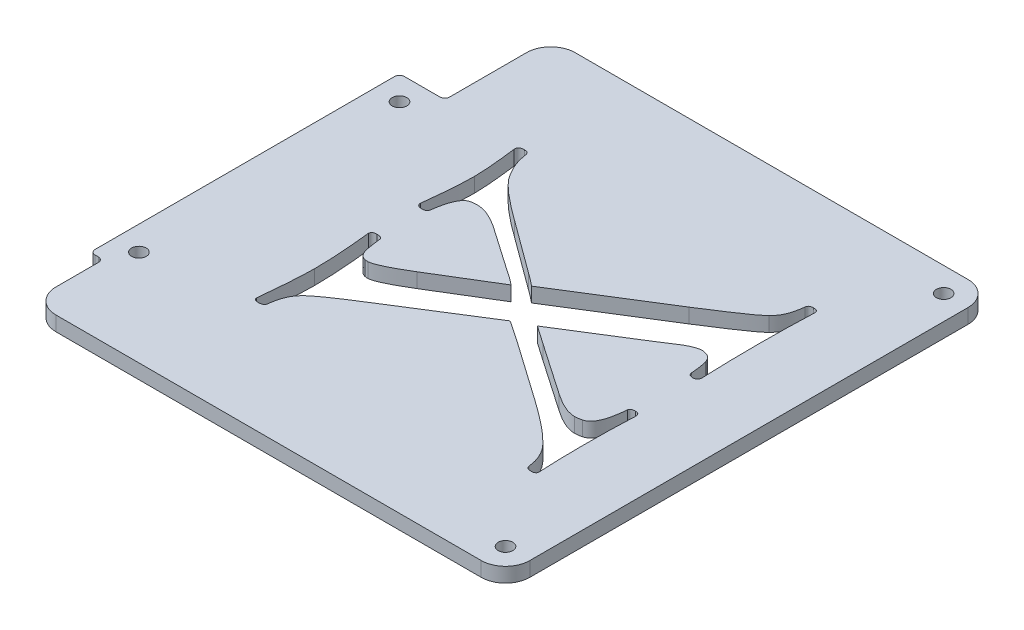
SolidWorks part; units mm, degrees
ref_plane "Front Plane" through (0, 0, 0) normal (0, 0, 1) x (1, 0, 0)
ref_plane "Top Plane" through (0, 0, 0) normal (0, 1, 0) x (1, 0, 0)
ref_plane "Right Plane" through (0, 0, 0) normal (1, 0, 0) x (0, 0, -1)
ref_plane "Plane1" through (0, 23, 0) normal (0, 1, 0) x (1, 0, 0)
sketch "Sketch1" plane through (0, 23, 0) normal (0, 1, 0) x (1, 0, 0)
  line L0 (98.3054, 50) -> (98.3054, 28.2195)
  line L1 (189, 50) -> (98.3054, 50)
  line L2 (189, 50) -> (189, -50)
  line L3 (189, -50) -> (97.6502, -50)
  line L5 (98.3054, 28.2195) -> (89, 28.2195)
  line L6 (89, 28.2195) -> (89, -35.308)
  line L7 (89, -35.308) -> (91.6598, -35.308)
  line L8 (91.6598, -35.308) -> (91.6598, -50)
  line L9 (91.6598, -50) -> (97.6502, -50)
  line L10 (94.8054, 33.2195) -> (98.3054, 33.2195) construction
  line L11 (184, 45) -> (184, 50) construction
  line L12 (93.3054, 31.7195) -> (93.3054, 28.2195) construction
  line L13 (99.4745, -35.308) -> (86.1225, -35.308) construction
  line L14 (88.1598, -40.308) -> (91.6598, -40.308) construction
  line L15 (86.6598, -38.808) -> (86.6598, -35.308) construction
  line L16 (189, 0) -> (190, 0) construction
  line L17 (190, -60) -> (190, 60) construction
  line L18 (105.0183, -40) -> (185.0183, -40) construction
  line L19 (105.0183, -40) -> (105.0183, 40) construction
  line L20 (105.0183, 40) -> (185.0183, 40) construction
  line L21 (185.0183, -40) -> (185.0183, 40) construction
  line L22 (184, 45) -> (189, 45) construction
  line L23 (184, -45) -> (189, -45) construction
  line L24 (184, -45) -> (184, -50) construction
  line L25 (94, 23.2195) -> (94, 28.2195) construction
  line L26 (94, 23.2195) -> (89, 23.2195) construction
  line L27 (94, -30.308) -> (94, -35.308) construction
  line L28 (94, -30.308) -> (89, -30.308) construction
  line L29 (190, -55) -> (190, 55) construction
  circle A0 centre (86.6598, -40.308) radius 1.5 construction
  circle A1 centre (93.3054, 33.2195) radius 1.5 construction
  circle A2 centre (184, 45) radius 1.5 construction
  circle A3 centre (184, 45) radius 1.5 construction
  circle A4 centre (184, -45) radius 1.5 construction
  circle A6 centre (94, 23.2195) radius 1.5 construction
  circle A7 centre (94, -30.308) radius 1.5 construction
  point P32 (185.0183, 0)
  dimension "D1" = 100
  dimension "D2" = 80
  dimension "D3" = 3.5
  dimension "D4" = 5
  dimension "D5" = 1
  dimension "D6" = 100
extrude "Boss-Extrude1" add sketch "Sketch1" along normal blind 3
fillet "Fillet3" radius 5 4 edges at (189, 24.5, -50) (98.3054, 24.5, -50) (91.6598, 24.5, 50) (189, 24.5, 50)
fillet "Fillet2" radius 1 4 edges at (89, 24.5, -28.2195) (98.3054, 24.5, -28.2195) (91.6598, 24.5, 35.308) (89, 24.5, 35.308)
sketch "Sketch2" plane through (0, 23, 0) normal (0, 1, 0) x (1, 0, 0)
  circle A0 centre (184, -45) radius 1.5 construction
  circle A1 centre (184, -45) radius 1.5
  circle A2 centre (94, -30.308) radius 1.5 construction
  circle A3 centre (94, -30.308) radius 1.5
  circle A4 centre (94, 23.2195) radius 1.5 construction
  circle A5 centre (94, 23.2195) radius 1.5
  circle A6 centre (184, 45) radius 1.5 construction
  circle A7 centre (184, 45) radius 1.5
extrude "Cut-Extrude1" cut sketch "Sketch2" along normal up to surface (3 mm away) up to face at (116.9913, 26, 1.7721)
sketch "Sketch4" plane through (0, 23, 0) normal (0, 1, 0) x (1, 0, 0)
  line L0 (176.5151, -28.0588) -> (176.5151, 28.0588) construction
  line L2 (150, 0) -> (182, 0) construction
  text T0 "X" font "@Yu Mincho Demibold" height 60
  point P3 (176.5151, 0)
extrude "Cut-Extrude2" cut sketch "Sketch4" along normal up to surface (3 mm away) up to face at (184, 26, 43.5)
